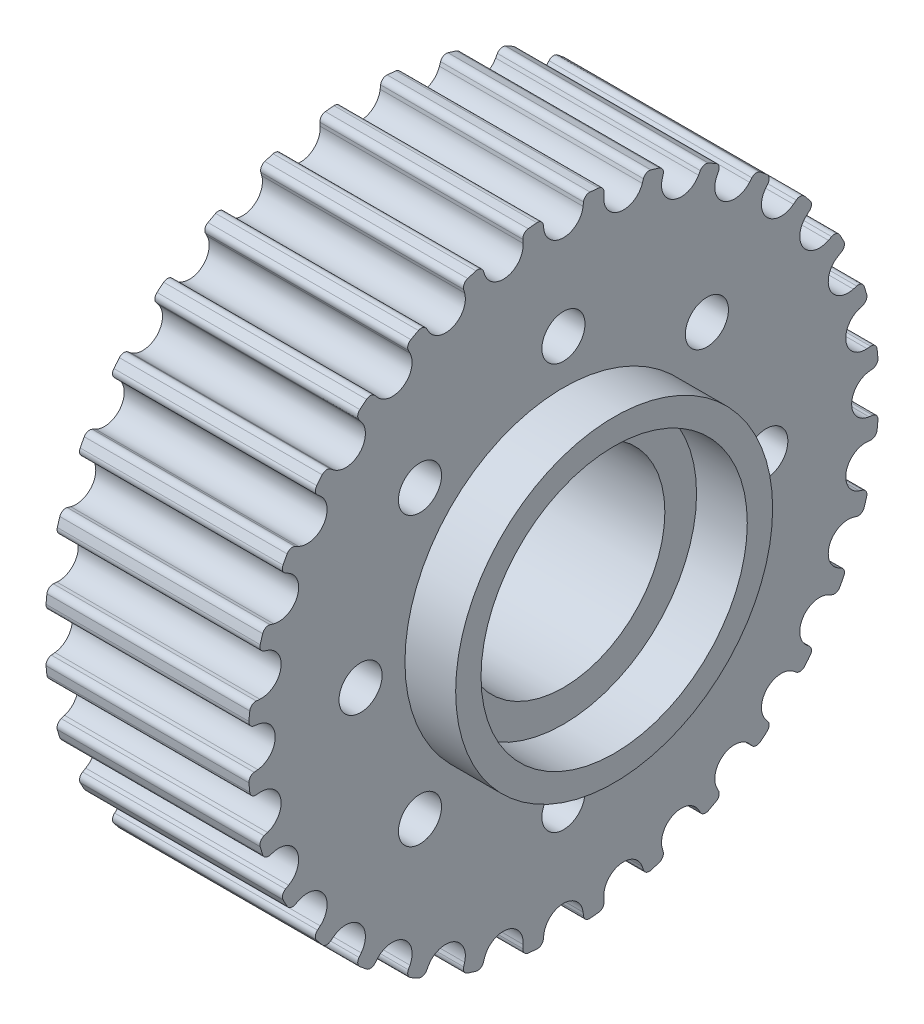
SolidWorks part; units mm, degrees
ref_plane "前视基准面" through (0, 0, 0) normal (0, 0, 1) x (1, 0, 0)
ref_plane "上视基准面" through (0, 0, 0) normal (0, 1, 0) x (1, 0, 0)
ref_plane "右视基准面" through (0, 0, 0) normal (1, 0, 0) x (0, 0, -1)
sketch "草图1" plane through (0, 0, 0) normal (0, 0, 1) x (1, 0, 0)
  line L0 (0, 0) -> (64.8368, 0) construction
  line L1 (0, 2.7506) -> (0, 24.893)
  line L2 (0, 24.893) -> (16, 24.893)
  line L3 (16, 24.893) -> (16, 5.5012)
  line L4 (16, 5.5012) -> (20, 5.5012)
  line L5 (20, 5.5012) -> (20, 2.7506)
  line L6 (20, 2.7506) -> (0, 2.7506)
  dimension "L" = 20
  dimension "B" = 16
  dimension "d" = 5.5012
  dimension "d1" = 11.0024
  dimension "da" = 49.786
revolve "旋转1" add sketch "草图1" angle 360 about L0
ref_axis "基准轴1" through (-1, 0, 0) along (1, 0, 0)
sketch "草图6" plane through (0, 0, 0) normal (1, 0, 0) x (0, 0, -1)
  line L0 (0, 0) -> (0, 30.6512) construction
  line L1 (1.5829, 24.3845) -> (1.5484, 24.1029)
  line L2 (2.5777, 24.7592) -> (2.7744, 26.3607)
  line L3 (-2.5777, 24.7592) -> (-2.7744, 26.3607)
  line L4 (-1.5829, 24.3845) -> (-1.5484, 24.1029)
  circle A0 centre (0, 0) radius 24.893 construction
  circle A1 centre (0, 0) radius 22.733 construction
  arc A2 (-1.5484, 24.1029) -> (1.5484, 24.1029) centre (0, 24.293) ccw
  arc A3 (2.7744, 26.3607) -> (-2.7744, 26.3607) centre (0, 0) ccw
  arc A4 (1.5829, 24.3845) -> (2.0999, 24.8043) centre (2.0594, 24.326) cw
  arc A5 (2.0999, 24.8043) -> (2.5777, 24.7592) centre (0, 0) cw
  arc A6 (-2.0999, 24.8043) -> (-2.5777, 24.7592) centre (0, 0) ccw
  arc A7 (-1.5829, 24.3845) -> (-2.0999, 24.8043) centre (-2.0594, 24.326) ccw
  point P7 (0, 3.25)
  point P8 (0, 28.4912)
  point P15 (1.6388, 24.839)
  dimension "D1" = 45.466
  dimension "ra" = 0.48
  dimension "rf" = 1.56
  dimension "hg" = 2.16
  dimension "D3" = 0.48
  dimension "D4" = 1.6136
  dimension "angle" = 14
  dimension "bw" = 3.25
extrude "切除-拉伸2" cut sketch "草图6" along normal up to next
pattern_circular "阵列(圆周)3" count 32 over 360 about axis through (-1, 0, 0) along (1, 0, 0) of "切除-拉伸2"
sketch "草图8" plane through (16, 0, 0) normal (1, 0, 0) x (0, 0, -1)
  line L64 (1.5829, 24.3845) -> (1.5484, 24.1029)
  line L65 (-1.5484, 24.1029) -> (-1.5829, 24.3845)
  line L66 (-3.2046, 24.2248) -> (-3.1836, 23.9418)
  line L67 (-6.2209, 23.3377) -> (-6.3097, 23.6071)
  line L68 (-7.8691, 23.1341) -> (-7.7933, 22.8607)
  line L69 (-10.6543, 21.6756) -> (-10.794, 21.9226)
  line L70 (-12.2311, 21.1544) -> (-12.1034, 20.901)
  line L71 (-14.6783, 19.1806) -> (-14.8635, 19.3955)
  line L72 (-16.1231, 18.3617) -> (-15.9484, 18.1382)
  line L73 (-18.1382, 15.9484) -> (-18.3617, 16.1231)
  line L74 (-19.3955, 14.8635) -> (-19.1806, 14.6783)
  line L75 (-20.901, 12.1034) -> (-21.1544, 12.2311)
  line L76 (-21.9226, 10.794) -> (-21.6756, 10.6543)
  line L77 (-22.8607, 7.7933) -> (-23.1341, 7.8691)
  line L78 (-23.6071, 6.3097) -> (-23.3377, 6.2209)
  line L79 (-23.9418, 3.1836) -> (-24.2248, 3.2046)
  line L80 (-24.3845, 1.5829) -> (-24.1029, 1.5484)
  line L81 (-24.1029, -1.5484) -> (-24.3845, -1.5829)
  line L82 (-24.2248, -3.2046) -> (-23.9418, -3.1836)
  line L83 (-23.3377, -6.2209) -> (-23.6071, -6.3097)
  line L84 (-23.1341, -7.8691) -> (-22.8607, -7.7933)
  line L85 (-21.6756, -10.6543) -> (-21.9226, -10.794)
  line L86 (-21.1544, -12.2311) -> (-20.901, -12.1034)
  line L87 (-19.1806, -14.6783) -> (-19.3955, -14.8635)
  line L88 (-18.3617, -16.1231) -> (-18.1382, -15.9484)
  line L89 (-15.9484, -18.1382) -> (-16.1231, -18.3617)
  line L90 (-14.8635, -19.3955) -> (-14.6783, -19.1806)
  line L91 (-12.1034, -20.901) -> (-12.2311, -21.1544)
  line L92 (-10.794, -21.9226) -> (-10.6543, -21.6756)
  line L93 (-7.7933, -22.8607) -> (-7.8691, -23.1341)
  line L94 (-6.3097, -23.6071) -> (-6.2209, -23.3377)
  line L95 (-3.1836, -23.9418) -> (-3.2046, -24.2248)
  line L96 (-1.5829, -24.3845) -> (-1.5484, -24.1029)
  line L97 (1.5484, -24.1029) -> (1.5829, -24.3845)
  line L98 (3.2046, -24.2248) -> (3.1836, -23.9418)
  line L99 (6.2209, -23.3377) -> (6.3097, -23.6071)
  line L100 (7.8691, -23.1341) -> (7.7933, -22.8607)
  line L101 (10.6543, -21.6756) -> (10.794, -21.9226)
  line L102 (12.2311, -21.1544) -> (12.1034, -20.901)
  line L103 (14.6783, -19.1806) -> (14.8635, -19.3955)
  line L104 (16.1231, -18.3617) -> (15.9484, -18.1382)
  line L105 (18.1382, -15.9484) -> (18.3617, -16.1231)
  line L106 (19.3955, -14.8635) -> (19.1806, -14.6783)
  line L107 (20.901, -12.1034) -> (21.1544, -12.2311)
  line L108 (21.9226, -10.794) -> (21.6756, -10.6543)
  line L109 (22.8607, -7.7933) -> (23.1341, -7.8691)
  line L110 (23.6071, -6.3097) -> (23.3377, -6.2209)
  line L111 (23.9418, -3.1836) -> (24.2248, -3.2046)
  line L112 (24.3845, -1.5829) -> (24.1029, -1.5484)
  line L113 (24.1029, 1.5484) -> (24.3845, 1.5829)
  line L114 (24.2248, 3.2046) -> (23.9418, 3.1836)
  line L115 (23.3377, 6.2209) -> (23.6071, 6.3097)
  line L116 (23.1341, 7.8691) -> (22.8607, 7.7933)
  line L117 (21.6756, 10.6543) -> (21.9226, 10.794)
  line L118 (21.1544, 12.2311) -> (20.901, 12.1034)
  line L119 (19.1806, 14.6783) -> (19.3955, 14.8635)
  line L120 (18.3617, 16.1231) -> (18.1382, 15.9484)
  line L121 (15.9484, 18.1382) -> (16.1231, 18.3617)
  line L122 (14.8635, 19.3955) -> (14.6783, 19.1806)
  line L123 (12.1034, 20.901) -> (12.2311, 21.1544)
  line L124 (10.794, 21.9226) -> (10.6543, 21.6756)
  line L125 (7.7933, 22.8607) -> (7.8691, 23.1341)
  line L126 (6.3097, 23.6071) -> (6.2209, 23.3377)
  line L127 (3.1836, 23.9418) -> (3.2046, 24.2248)
  line L128 (1.5829, 24.3845) -> (1.5484, 24.1029)
  line L129 (-1.5484, 24.1029) -> (-1.5829, 24.3845)
  line L130 (-3.2046, 24.2248) -> (-3.1836, 23.9418)
  line L131 (-6.2209, 23.3377) -> (-6.3097, 23.6071)
  line L132 (-7.8691, 23.1341) -> (-7.7933, 22.8607)
  line L133 (-10.6543, 21.6756) -> (-10.794, 21.9226)
  line L134 (-12.2311, 21.1544) -> (-12.1034, 20.901)
  line L135 (-14.6783, 19.1806) -> (-14.8635, 19.3955)
  line L136 (-16.1231, 18.3617) -> (-15.9484, 18.1382)
  line L137 (-18.1382, 15.9484) -> (-18.3617, 16.1231)
  line L138 (-19.3955, 14.8635) -> (-19.1806, 14.6783)
  line L139 (-20.901, 12.1034) -> (-21.1544, 12.2311)
  line L140 (-21.9226, 10.794) -> (-21.6756, 10.6543)
  line L141 (-22.8607, 7.7933) -> (-23.1341, 7.8691)
  line L142 (-23.6071, 6.3097) -> (-23.3377, 6.2209)
  line L143 (-23.9418, 3.1836) -> (-24.2248, 3.2046)
  line L144 (-24.3845, 1.5829) -> (-24.1029, 1.5484)
  line L145 (-24.1029, -1.5484) -> (-24.3845, -1.5829)
  line L146 (-24.2248, -3.2046) -> (-23.9418, -3.1836)
  line L147 (-23.3377, -6.2209) -> (-23.6071, -6.3097)
  line L148 (-23.1341, -7.8691) -> (-22.8607, -7.7933)
  line L149 (-21.6756, -10.6543) -> (-21.9226, -10.794)
  line L150 (-21.1544, -12.2311) -> (-20.901, -12.1034)
  line L151 (-19.1806, -14.6783) -> (-19.3955, -14.8635)
  line L152 (-18.3617, -16.1231) -> (-18.1382, -15.9484)
  line L153 (-15.9484, -18.1382) -> (-16.1231, -18.3617)
  line L154 (-14.8635, -19.3955) -> (-14.6783, -19.1806)
  line L155 (-12.1034, -20.901) -> (-12.2311, -21.1544)
  line L156 (-10.794, -21.9226) -> (-10.6543, -21.6756)
  line L157 (-7.7933, -22.8607) -> (-7.8691, -23.1341)
  line L158 (-6.3097, -23.6071) -> (-6.2209, -23.3377)
  line L159 (-3.1836, -23.9418) -> (-3.2046, -24.2248)
  line L160 (-1.5829, -24.3845) -> (-1.5484, -24.1029)
  line L161 (1.5484, -24.1029) -> (1.5829, -24.3845)
  line L162 (3.2046, -24.2248) -> (3.1836, -23.9418)
  line L163 (6.2209, -23.3377) -> (6.3097, -23.6071)
  line L164 (7.8691, -23.1341) -> (7.7933, -22.8607)
  line L165 (10.6543, -21.6756) -> (10.794, -21.9226)
  line L166 (12.2311, -21.1544) -> (12.1034, -20.901)
  line L167 (14.6783, -19.1806) -> (14.8635, -19.3955)
  line L168 (16.1231, -18.3617) -> (15.9484, -18.1382)
  line L169 (18.1382, -15.9484) -> (18.3617, -16.1231)
  line L170 (19.3955, -14.8635) -> (19.1806, -14.6783)
  line L171 (20.901, -12.1034) -> (21.1544, -12.2311)
  line L172 (21.9226, -10.794) -> (21.6756, -10.6543)
  line L173 (22.8607, -7.7933) -> (23.1341, -7.8691)
  line L174 (23.6071, -6.3097) -> (23.3377, -6.2209)
  line L175 (23.9418, -3.1836) -> (24.2248, -3.2046)
  line L176 (24.3845, -1.5829) -> (24.1029, -1.5484)
  line L177 (24.1029, 1.5484) -> (24.3845, 1.5829)
  line L178 (24.2248, 3.2046) -> (23.9418, 3.1836)
  line L179 (23.3377, 6.2209) -> (23.6071, 6.3097)
  line L180 (23.1341, 7.8691) -> (22.8607, 7.7933)
  line L181 (21.6756, 10.6543) -> (21.9226, 10.794)
  line L182 (21.1544, 12.2311) -> (20.901, 12.1034)
  line L183 (19.1806, 14.6783) -> (19.3955, 14.8635)
  line L184 (18.3617, 16.1231) -> (18.1382, 15.9484)
  line L185 (15.9484, 18.1382) -> (16.1231, 18.3617)
  line L186 (14.8635, 19.3955) -> (14.6783, 19.1806)
  line L187 (12.1034, 20.901) -> (12.2311, 21.1544)
  line L188 (10.794, 21.9226) -> (10.6543, 21.6756)
  line L189 (7.7933, 22.8607) -> (7.8691, 23.1341)
  line L190 (6.3097, 23.6071) -> (6.2209, 23.3377)
  line L191 (3.1836, 23.9418) -> (3.2046, 24.2248)
  circle A0 centre (0, 0) radius 12.5
  arc A128 (3.2046, 24.2248) -> (2.7796, 24.7373) centre (2.726, 24.2603) ccw
  arc A129 (2.7796, 24.7373) -> (2.0999, 24.8043) centre (0, 0) ccw
  arc A130 (2.0999, 24.8043) -> (1.5829, 24.3845) centre (2.0594, 24.326) ccw
  arc A131 (-1.5484, 24.1029) -> (1.5484, 24.1029) centre (0, 24.293) ccw
  arc A132 (-1.5829, 24.3845) -> (-2.0999, 24.8043) centre (-2.0594, 24.326) ccw
  arc A133 (-2.0999, 24.8043) -> (-2.7796, 24.7373) centre (0, 0) ccw
  arc A134 (-2.7796, 24.7373) -> (-3.2046, 24.2248) centre (-2.726, 24.2603) ccw
  arc A135 (-6.2209, 23.3377) -> (-3.1836, 23.9418) centre (-4.7393, 23.8262) ccw
  arc A136 (-6.3097, 23.6071) -> (-6.8986, 23.918) centre (-6.7656, 23.4568) ccw
  arc A137 (-6.8986, 23.918) -> (-7.5522, 23.7197) centre (0, 0) ccw
  arc A138 (-7.5522, 23.7197) -> (-7.8691, 23.1341) centre (-7.4065, 23.2624) ccw
  arc A139 (-10.6543, 21.6756) -> (-7.7933, 22.8607) centre (-9.2965, 22.4438) ccw
  arc A140 (-10.794, 21.9226) -> (-11.4322, 22.1126) centre (-11.2118, 21.6862) ccw
  arc A141 (-11.4322, 22.1126) -> (-12.0345, 21.7906) centre (0, 0) ccw
  arc A142 (-12.0345, 21.7906) -> (-12.2311, 21.1544) centre (-11.8025, 21.3704) ccw
  arc A143 (-14.6783, 19.1806) -> (-12.1034, 20.901) centre (-13.4965, 20.1989) ccw
  arc A144 (-14.8635, 19.3955) -> (-15.5265, 19.4574) centre (-15.2271, 19.0822) ccw
  arc A145 (-15.5265, 19.4574) -> (-16.0544, 19.0241) centre (0, 0) ccw
  arc A146 (-16.0544, 19.0241) -> (-16.1231, 18.3617) centre (-15.7449, 18.6573) ccw
  arc A147 (-18.1382, 15.9484) -> (-15.9484, 18.1382) centre (-17.1777, 17.1777) ccw
  arc A148 (-18.3617, 16.1231) -> (-19.0241, 16.0544) centre (-18.6573, 15.7449) ccw
  arc A149 (-19.0241, 16.0544) -> (-19.4574, 15.5265) centre (0, 0) ccw
  arc A150 (-19.4574, 15.5265) -> (-19.3955, 14.8635) centre (-19.0822, 15.2271) ccw
  arc A151 (-20.901, 12.1034) -> (-19.1806, 14.6783) centre (-20.1989, 13.4965) ccw
  arc A152 (-21.1544, 12.2311) -> (-21.7906, 12.0345) centre (-21.3704, 11.8025) ccw
  arc A153 (-21.7906, 12.0345) -> (-22.1126, 11.4322) centre (0, 0) ccw
  arc A154 (-22.1126, 11.4322) -> (-21.9226, 10.794) centre (-21.6862, 11.2118) ccw
  arc A155 (-22.8607, 7.7933) -> (-21.6756, 10.6543) centre (-22.4438, 9.2965) ccw
  arc A156 (-23.1341, 7.8691) -> (-23.7197, 7.5522) centre (-23.2624, 7.4065) ccw
  arc A157 (-23.7197, 7.5522) -> (-23.918, 6.8986) centre (0, 0) ccw
  arc A158 (-23.918, 6.8986) -> (-23.6071, 6.3097) centre (-23.4568, 6.7656) ccw
  arc A159 (-23.9418, 3.1836) -> (-23.3377, 6.2209) centre (-23.8262, 4.7393) ccw
  arc A160 (-24.2248, 3.2046) -> (-24.7373, 2.7796) centre (-24.2603, 2.726) ccw
  arc A161 (-24.7373, 2.7796) -> (-24.8043, 2.0999) centre (0, 0) ccw
  arc A162 (-24.8043, 2.0999) -> (-24.3845, 1.5829) centre (-24.326, 2.0594) ccw
  arc A163 (-24.1029, -1.5484) -> (-24.1029, 1.5484) centre (-24.293, 0) ccw
  arc A164 (-24.3845, -1.5829) -> (-24.8043, -2.0999) centre (-24.326, -2.0594) ccw
  arc A165 (-24.8043, -2.0999) -> (-24.7373, -2.7796) centre (0, 0) ccw
  arc A166 (-24.7373, -2.7796) -> (-24.2248, -3.2046) centre (-24.2603, -2.726) ccw
  arc A167 (-23.3377, -6.2209) -> (-23.9418, -3.1836) centre (-23.8262, -4.7393) ccw
  arc A168 (-23.6071, -6.3097) -> (-23.918, -6.8986) centre (-23.4568, -6.7656) ccw
  arc A169 (-23.918, -6.8986) -> (-23.7197, -7.5522) centre (0, 0) ccw
  arc A170 (-23.7197, -7.5522) -> (-23.1341, -7.8691) centre (-23.2624, -7.4065) ccw
  arc A171 (-21.6756, -10.6543) -> (-22.8607, -7.7933) centre (-22.4438, -9.2965) ccw
  arc A172 (-21.9226, -10.794) -> (-22.1126, -11.4322) centre (-21.6862, -11.2118) ccw
  arc A173 (-22.1126, -11.4322) -> (-21.7906, -12.0345) centre (0, 0) ccw
  arc A174 (-21.7906, -12.0345) -> (-21.1544, -12.2311) centre (-21.3704, -11.8025) ccw
  arc A175 (-19.1806, -14.6783) -> (-20.901, -12.1034) centre (-20.1989, -13.4965) ccw
  arc A176 (-19.3955, -14.8635) -> (-19.4574, -15.5265) centre (-19.0822, -15.2271) ccw
  arc A177 (-19.4574, -15.5265) -> (-19.0241, -16.0544) centre (0, 0) ccw
  arc A178 (-19.0241, -16.0544) -> (-18.3617, -16.1231) centre (-18.6573, -15.7449) ccw
  arc A179 (-15.9484, -18.1382) -> (-18.1382, -15.9484) centre (-17.1777, -17.1777) ccw
  arc A180 (-16.1231, -18.3617) -> (-16.0544, -19.0241) centre (-15.7449, -18.6573) ccw
  arc A181 (-16.0544, -19.0241) -> (-15.5265, -19.4574) centre (0, 0) ccw
  arc A182 (-15.5265, -19.4574) -> (-14.8635, -19.3955) centre (-15.2271, -19.0822) ccw
  arc A183 (-12.1034, -20.901) -> (-14.6783, -19.1806) centre (-13.4965, -20.1989) ccw
  arc A184 (-12.2311, -21.1544) -> (-12.0345, -21.7906) centre (-11.8025, -21.3704) ccw
  arc A185 (-12.0345, -21.7906) -> (-11.4322, -22.1126) centre (0, 0) ccw
  arc A186 (-11.4322, -22.1126) -> (-10.794, -21.9226) centre (-11.2118, -21.6862) ccw
  arc A187 (-7.7933, -22.8607) -> (-10.6543, -21.6756) centre (-9.2965, -22.4438) ccw
  arc A188 (-7.8691, -23.1341) -> (-7.5522, -23.7197) centre (-7.4065, -23.2624) ccw
  arc A189 (-7.5522, -23.7197) -> (-6.8986, -23.918) centre (0, 0) ccw
  arc A190 (-6.8986, -23.918) -> (-6.3097, -23.6071) centre (-6.7656, -23.4568) ccw
  arc A191 (-3.1836, -23.9418) -> (-6.2209, -23.3377) centre (-4.7393, -23.8262) ccw
  arc A192 (-3.2046, -24.2248) -> (-2.7796, -24.7373) centre (-2.726, -24.2603) ccw
  arc A193 (-2.7796, -24.7373) -> (-2.0999, -24.8043) centre (0, 0) ccw
  arc A194 (-2.0999, -24.8043) -> (-1.5829, -24.3845) centre (-2.0594, -24.326) ccw
  arc A195 (1.5484, -24.1029) -> (-1.5484, -24.1029) centre (0, -24.293) ccw
  arc A196 (1.5829, -24.3845) -> (2.0999, -24.8043) centre (2.0594, -24.326) ccw
  arc A197 (2.0999, -24.8043) -> (2.7796, -24.7373) centre (0, 0) ccw
  arc A198 (2.7796, -24.7373) -> (3.2046, -24.2248) centre (2.726, -24.2603) ccw
  arc A199 (6.2209, -23.3377) -> (3.1836, -23.9418) centre (4.7393, -23.8262) ccw
  arc A200 (6.3097, -23.6071) -> (6.8986, -23.918) centre (6.7656, -23.4568) ccw
  arc A201 (6.8986, -23.918) -> (7.5522, -23.7197) centre (0, 0) ccw
  arc A202 (7.5522, -23.7197) -> (7.8691, -23.1341) centre (7.4065, -23.2624) ccw
  arc A203 (10.6543, -21.6756) -> (7.7933, -22.8607) centre (9.2965, -22.4438) ccw
  arc A204 (10.794, -21.9226) -> (11.4322, -22.1126) centre (11.2118, -21.6862) ccw
  arc A205 (11.4322, -22.1126) -> (12.0345, -21.7906) centre (0, 0) ccw
  arc A206 (12.0345, -21.7906) -> (12.2311, -21.1544) centre (11.8025, -21.3704) ccw
  arc A207 (14.6783, -19.1806) -> (12.1034, -20.901) centre (13.4965, -20.1989) ccw
  arc A208 (14.8635, -19.3955) -> (15.5265, -19.4574) centre (15.2271, -19.0822) ccw
  arc A209 (15.5265, -19.4574) -> (16.0544, -19.0241) centre (0, 0) ccw
  arc A210 (16.0544, -19.0241) -> (16.1231, -18.3617) centre (15.7449, -18.6573) ccw
  arc A211 (18.1382, -15.9484) -> (15.9484, -18.1382) centre (17.1777, -17.1777) ccw
  arc A212 (18.3617, -16.1231) -> (19.0241, -16.0544) centre (18.6573, -15.7449) ccw
  arc A213 (19.0241, -16.0544) -> (19.4574, -15.5265) centre (0, 0) ccw
  arc A214 (19.4574, -15.5265) -> (19.3955, -14.8635) centre (19.0822, -15.2271) ccw
  arc A215 (20.901, -12.1034) -> (19.1806, -14.6783) centre (20.1989, -13.4965) ccw
  arc A216 (21.1544, -12.2311) -> (21.7906, -12.0345) centre (21.3704, -11.8025) ccw
  arc A217 (21.7906, -12.0345) -> (22.1126, -11.4322) centre (0, 0) ccw
  arc A218 (22.1126, -11.4322) -> (21.9226, -10.794) centre (21.6862, -11.2118) ccw
  arc A219 (22.8607, -7.7933) -> (21.6756, -10.6543) centre (22.4438, -9.2965) ccw
  arc A220 (23.1341, -7.8691) -> (23.7197, -7.5522) centre (23.2624, -7.4065) ccw
  arc A221 (23.7197, -7.5522) -> (23.918, -6.8986) centre (0, 0) ccw
  arc A222 (23.918, -6.8986) -> (23.6071, -6.3097) centre (23.4568, -6.7656) ccw
  arc A223 (23.9418, -3.1836) -> (23.3377, -6.2209) centre (23.8262, -4.7393) ccw
  arc A224 (24.2248, -3.2046) -> (24.7373, -2.7796) centre (24.2603, -2.726) ccw
  arc A225 (24.7373, -2.7796) -> (24.8043, -2.0999) centre (0, 0) ccw
  arc A226 (24.8043, -2.0999) -> (24.3845, -1.5829) centre (24.326, -2.0594) ccw
  arc A227 (24.1029, 1.5484) -> (24.1029, -1.5484) centre (24.293, 0) ccw
  arc A228 (24.3845, 1.5829) -> (24.8043, 2.0999) centre (24.326, 2.0594) ccw
  arc A229 (24.8043, 2.0999) -> (24.7373, 2.7796) centre (0, 0) ccw
  arc A230 (24.7373, 2.7796) -> (24.2248, 3.2046) centre (24.2603, 2.726) ccw
  arc A231 (23.3377, 6.2209) -> (23.9418, 3.1836) centre (23.8262, 4.7393) ccw
  arc A232 (23.6071, 6.3097) -> (23.918, 6.8986) centre (23.4568, 6.7656) ccw
  arc A233 (23.918, 6.8986) -> (23.7197, 7.5522) centre (0, 0) ccw
  arc A234 (23.7197, 7.5522) -> (23.1341, 7.8691) centre (23.2624, 7.4065) ccw
  arc A235 (21.6756, 10.6543) -> (22.8607, 7.7933) centre (22.4438, 9.2965) ccw
  arc A236 (21.9226, 10.794) -> (22.1126, 11.4322) centre (21.6862, 11.2118) ccw
  arc A237 (22.1126, 11.4322) -> (21.7906, 12.0345) centre (0, 0) ccw
  arc A238 (21.7906, 12.0345) -> (21.1544, 12.2311) centre (21.3704, 11.8025) ccw
  arc A239 (19.1806, 14.6783) -> (20.901, 12.1034) centre (20.1989, 13.4965) ccw
  arc A240 (19.3955, 14.8635) -> (19.4574, 15.5265) centre (19.0822, 15.2271) ccw
  arc A241 (19.4574, 15.5265) -> (19.0241, 16.0544) centre (0, 0) ccw
  arc A242 (19.0241, 16.0544) -> (18.3617, 16.1231) centre (18.6573, 15.7449) ccw
  arc A243 (15.9484, 18.1382) -> (18.1382, 15.9484) centre (17.1777, 17.1777) ccw
  arc A244 (16.1231, 18.3617) -> (16.0544, 19.0241) centre (15.7449, 18.6573) ccw
  arc A245 (16.0544, 19.0241) -> (15.5265, 19.4574) centre (0, 0) ccw
  arc A246 (15.5265, 19.4574) -> (14.8635, 19.3955) centre (15.2271, 19.0822) ccw
  arc A247 (12.1034, 20.901) -> (14.6783, 19.1806) centre (13.4965, 20.1989) ccw
  arc A248 (12.2311, 21.1544) -> (12.0345, 21.7906) centre (11.8025, 21.3704) ccw
  arc A249 (12.0345, 21.7906) -> (11.4322, 22.1126) centre (0, 0) ccw
  arc A250 (11.4322, 22.1126) -> (10.794, 21.9226) centre (11.2118, 21.6862) ccw
  arc A251 (7.7933, 22.8607) -> (10.6543, 21.6756) centre (9.2965, 22.4438) ccw
  arc A252 (7.8691, 23.1341) -> (7.5522, 23.7197) centre (7.4065, 23.2624) ccw
  arc A253 (7.5522, 23.7197) -> (6.8986, 23.918) centre (0, 0) ccw
  arc A254 (6.8986, 23.918) -> (6.3097, 23.6071) centre (6.7656, 23.4568) ccw
  arc A255 (3.1836, 23.9418) -> (6.2209, 23.3377) centre (4.7393, 23.8262) ccw
  arc A256 (3.2046, 24.2248) -> (2.7796, 24.7373) centre (2.726, 24.2603) ccw
  arc A257 (2.7796, 24.7373) -> (2.0999, 24.8043) centre (0, 0) ccw
  arc A258 (2.0999, 24.8043) -> (1.5829, 24.3845) centre (2.0594, 24.326) ccw
  arc A259 (-1.5484, 24.1029) -> (1.5484, 24.1029) centre (0, 24.293) ccw
  arc A260 (-1.5829, 24.3845) -> (-2.0999, 24.8043) centre (-2.0594, 24.326) ccw
  arc A261 (-2.0999, 24.8043) -> (-2.7796, 24.7373) centre (0, 0) ccw
  arc A262 (-2.7796, 24.7373) -> (-3.2046, 24.2248) centre (-2.726, 24.2603) ccw
  arc A263 (-6.2209, 23.3377) -> (-3.1836, 23.9418) centre (-4.7393, 23.8262) ccw
  arc A264 (-6.3097, 23.6071) -> (-6.8986, 23.918) centre (-6.7656, 23.4568) ccw
  arc A265 (-6.8986, 23.918) -> (-7.5522, 23.7197) centre (0, 0) ccw
  arc A266 (-7.5522, 23.7197) -> (-7.8691, 23.1341) centre (-7.4065, 23.2624) ccw
  arc A267 (-10.6543, 21.6756) -> (-7.7933, 22.8607) centre (-9.2965, 22.4438) ccw
  arc A268 (-10.794, 21.9226) -> (-11.4322, 22.1126) centre (-11.2118, 21.6862) ccw
  arc A269 (-11.4322, 22.1126) -> (-12.0345, 21.7906) centre (0, 0) ccw
  arc A270 (-12.0345, 21.7906) -> (-12.2311, 21.1544) centre (-11.8025, 21.3704) ccw
  arc A271 (-14.6783, 19.1806) -> (-12.1034, 20.901) centre (-13.4965, 20.1989) ccw
  arc A272 (-14.8635, 19.3955) -> (-15.5265, 19.4574) centre (-15.2271, 19.0822) ccw
  arc A273 (-15.5265, 19.4574) -> (-16.0544, 19.0241) centre (0, 0) ccw
  arc A274 (-16.0544, 19.0241) -> (-16.1231, 18.3617) centre (-15.7449, 18.6573) ccw
  arc A275 (-18.1382, 15.9484) -> (-15.9484, 18.1382) centre (-17.1777, 17.1777) ccw
  arc A276 (-18.3617, 16.1231) -> (-19.0241, 16.0544) centre (-18.6573, 15.7449) ccw
  arc A277 (-19.0241, 16.0544) -> (-19.4574, 15.5265) centre (0, 0) ccw
  arc A278 (-19.4574, 15.5265) -> (-19.3955, 14.8635) centre (-19.0822, 15.2271) ccw
  arc A279 (-20.901, 12.1034) -> (-19.1806, 14.6783) centre (-20.1989, 13.4965) ccw
  arc A280 (-21.1544, 12.2311) -> (-21.7906, 12.0345) centre (-21.3704, 11.8025) ccw
  arc A281 (-21.7906, 12.0345) -> (-22.1126, 11.4322) centre (0, 0) ccw
  arc A282 (-22.1126, 11.4322) -> (-21.9226, 10.794) centre (-21.6862, 11.2118) ccw
  arc A283 (-22.8607, 7.7933) -> (-21.6756, 10.6543) centre (-22.4438, 9.2965) ccw
  arc A284 (-23.1341, 7.8691) -> (-23.7197, 7.5522) centre (-23.2624, 7.4065) ccw
  arc A285 (-23.7197, 7.5522) -> (-23.918, 6.8986) centre (0, 0) ccw
  arc A286 (-23.918, 6.8986) -> (-23.6071, 6.3097) centre (-23.4568, 6.7656) ccw
  arc A287 (-23.9418, 3.1836) -> (-23.3377, 6.2209) centre (-23.8262, 4.7393) ccw
  arc A288 (-24.2248, 3.2046) -> (-24.7373, 2.7796) centre (-24.2603, 2.726) ccw
  arc A289 (-24.7373, 2.7796) -> (-24.8043, 2.0999) centre (0, 0) ccw
  arc A290 (-24.8043, 2.0999) -> (-24.3845, 1.5829) centre (-24.326, 2.0594) ccw
  arc A291 (-24.1029, -1.5484) -> (-24.1029, 1.5484) centre (-24.293, 0) ccw
  arc A292 (-24.3845, -1.5829) -> (-24.8043, -2.0999) centre (-24.326, -2.0594) ccw
  arc A293 (-24.8043, -2.0999) -> (-24.7373, -2.7796) centre (0, 0) ccw
  arc A294 (-24.7373, -2.7796) -> (-24.2248, -3.2046) centre (-24.2603, -2.726) ccw
  arc A295 (-23.3377, -6.2209) -> (-23.9418, -3.1836) centre (-23.8262, -4.7393) ccw
  arc A296 (-23.6071, -6.3097) -> (-23.918, -6.8986) centre (-23.4568, -6.7656) ccw
  arc A297 (-23.918, -6.8986) -> (-23.7197, -7.5522) centre (0, 0) ccw
  arc A298 (-23.7197, -7.5522) -> (-23.1341, -7.8691) centre (-23.2624, -7.4065) ccw
  arc A299 (-21.6756, -10.6543) -> (-22.8607, -7.7933) centre (-22.4438, -9.2965) ccw
  arc A300 (-21.9226, -10.794) -> (-22.1126, -11.4322) centre (-21.6862, -11.2118) ccw
  arc A301 (-22.1126, -11.4322) -> (-21.7906, -12.0345) centre (0, 0) ccw
  arc A302 (-21.7906, -12.0345) -> (-21.1544, -12.2311) centre (-21.3704, -11.8025) ccw
  arc A303 (-19.1806, -14.6783) -> (-20.901, -12.1034) centre (-20.1989, -13.4965) ccw
  arc A304 (-19.3955, -14.8635) -> (-19.4574, -15.5265) centre (-19.0822, -15.2271) ccw
  arc A305 (-19.4574, -15.5265) -> (-19.0241, -16.0544) centre (0, 0) ccw
  arc A306 (-19.0241, -16.0544) -> (-18.3617, -16.1231) centre (-18.6573, -15.7449) ccw
  arc A307 (-15.9484, -18.1382) -> (-18.1382, -15.9484) centre (-17.1777, -17.1777) ccw
  arc A308 (-16.1231, -18.3617) -> (-16.0544, -19.0241) centre (-15.7449, -18.6573) ccw
  arc A309 (-16.0544, -19.0241) -> (-15.5265, -19.4574) centre (0, 0) ccw
  arc A310 (-15.5265, -19.4574) -> (-14.8635, -19.3955) centre (-15.2271, -19.0822) ccw
  arc A311 (-12.1034, -20.901) -> (-14.6783, -19.1806) centre (-13.4965, -20.1989) ccw
  arc A312 (-12.2311, -21.1544) -> (-12.0345, -21.7906) centre (-11.8025, -21.3704) ccw
  arc A313 (-12.0345, -21.7906) -> (-11.4322, -22.1126) centre (0, 0) ccw
  arc A314 (-11.4322, -22.1126) -> (-10.794, -21.9226) centre (-11.2118, -21.6862) ccw
  arc A315 (-7.7933, -22.8607) -> (-10.6543, -21.6756) centre (-9.2965, -22.4438) ccw
  arc A316 (-7.8691, -23.1341) -> (-7.5522, -23.7197) centre (-7.4065, -23.2624) ccw
  arc A317 (-7.5522, -23.7197) -> (-6.8986, -23.918) centre (0, 0) ccw
  arc A318 (-6.8986, -23.918) -> (-6.3097, -23.6071) centre (-6.7656, -23.4568) ccw
  arc A319 (-3.1836, -23.9418) -> (-6.2209, -23.3377) centre (-4.7393, -23.8262) ccw
  arc A320 (-3.2046, -24.2248) -> (-2.7796, -24.7373) centre (-2.726, -24.2603) ccw
  arc A321 (-2.7796, -24.7373) -> (-2.0999, -24.8043) centre (0, 0) ccw
  arc A322 (-2.0999, -24.8043) -> (-1.5829, -24.3845) centre (-2.0594, -24.326) ccw
  arc A323 (1.5484, -24.1029) -> (-1.5484, -24.1029) centre (0, -24.293) ccw
  arc A324 (1.5829, -24.3845) -> (2.0999, -24.8043) centre (2.0594, -24.326) ccw
  arc A325 (2.0999, -24.8043) -> (2.7796, -24.7373) centre (0, 0) ccw
  arc A326 (2.7796, -24.7373) -> (3.2046, -24.2248) centre (2.726, -24.2603) ccw
  arc A327 (6.2209, -23.3377) -> (3.1836, -23.9418) centre (4.7393, -23.8262) ccw
  arc A328 (6.3097, -23.6071) -> (6.8986, -23.918) centre (6.7656, -23.4568) ccw
  arc A329 (6.8986, -23.918) -> (7.5522, -23.7197) centre (0, 0) ccw
  arc A330 (7.5522, -23.7197) -> (7.8691, -23.1341) centre (7.4065, -23.2624) ccw
  arc A331 (10.6543, -21.6756) -> (7.7933, -22.8607) centre (9.2965, -22.4438) ccw
  arc A332 (10.794, -21.9226) -> (11.4322, -22.1126) centre (11.2118, -21.6862) ccw
  arc A333 (11.4322, -22.1126) -> (12.0345, -21.7906) centre (0, 0) ccw
  arc A334 (12.0345, -21.7906) -> (12.2311, -21.1544) centre (11.8025, -21.3704) ccw
  arc A335 (14.6783, -19.1806) -> (12.1034, -20.901) centre (13.4965, -20.1989) ccw
  arc A336 (14.8635, -19.3955) -> (15.5265, -19.4574) centre (15.2271, -19.0822) ccw
  arc A337 (15.5265, -19.4574) -> (16.0544, -19.0241) centre (0, 0) ccw
  arc A338 (16.0544, -19.0241) -> (16.1231, -18.3617) centre (15.7449, -18.6573) ccw
  arc A339 (18.1382, -15.9484) -> (15.9484, -18.1382) centre (17.1777, -17.1777) ccw
  arc A340 (18.3617, -16.1231) -> (19.0241, -16.0544) centre (18.6573, -15.7449) ccw
  arc A341 (19.0241, -16.0544) -> (19.4574, -15.5265) centre (0, 0) ccw
  arc A342 (19.4574, -15.5265) -> (19.3955, -14.8635) centre (19.0822, -15.2271) ccw
  arc A343 (20.901, -12.1034) -> (19.1806, -14.6783) centre (20.1989, -13.4965) ccw
  arc A344 (21.1544, -12.2311) -> (21.7906, -12.0345) centre (21.3704, -11.8025) ccw
  arc A345 (21.7906, -12.0345) -> (22.1126, -11.4322) centre (0, 0) ccw
  arc A346 (22.1126, -11.4322) -> (21.9226, -10.794) centre (21.6862, -11.2118) ccw
  arc A347 (22.8607, -7.7933) -> (21.6756, -10.6543) centre (22.4438, -9.2965) ccw
  arc A348 (23.1341, -7.8691) -> (23.7197, -7.5522) centre (23.2624, -7.4065) ccw
  arc A349 (23.7197, -7.5522) -> (23.918, -6.8986) centre (0, 0) ccw
  arc A350 (23.918, -6.8986) -> (23.6071, -6.3097) centre (23.4568, -6.7656) ccw
  arc A351 (23.9418, -3.1836) -> (23.3377, -6.2209) centre (23.8262, -4.7393) ccw
  arc A352 (24.2248, -3.2046) -> (24.7373, -2.7796) centre (24.2603, -2.726) ccw
  arc A353 (24.7373, -2.7796) -> (24.8043, -2.0999) centre (0, 0) ccw
  arc A354 (24.8043, -2.0999) -> (24.3845, -1.5829) centre (24.326, -2.0594) ccw
  arc A355 (24.1029, 1.5484) -> (24.1029, -1.5484) centre (24.293, 0) ccw
  arc A356 (24.3845, 1.5829) -> (24.8043, 2.0999) centre (24.326, 2.0594) ccw
  arc A357 (24.8043, 2.0999) -> (24.7373, 2.7796) centre (0, 0) ccw
  arc A358 (24.7373, 2.7796) -> (24.2248, 3.2046) centre (24.2603, 2.726) ccw
  arc A359 (23.3377, 6.2209) -> (23.9418, 3.1836) centre (23.8262, 4.7393) ccw
  arc A360 (23.6071, 6.3097) -> (23.918, 6.8986) centre (23.4568, 6.7656) ccw
  arc A361 (23.918, 6.8986) -> (23.7197, 7.5522) centre (0, 0) ccw
  arc A362 (23.7197, 7.5522) -> (23.1341, 7.8691) centre (23.2624, 7.4065) ccw
  arc A363 (21.6756, 10.6543) -> (22.8607, 7.7933) centre (22.4438, 9.2965) ccw
  arc A364 (21.9226, 10.794) -> (22.1126, 11.4322) centre (21.6862, 11.2118) ccw
  arc A365 (22.1126, 11.4322) -> (21.7906, 12.0345) centre (0, 0) ccw
  arc A366 (21.7906, 12.0345) -> (21.1544, 12.2311) centre (21.3704, 11.8025) ccw
  arc A367 (19.1806, 14.6783) -> (20.901, 12.1034) centre (20.1989, 13.4965) ccw
  arc A368 (19.3955, 14.8635) -> (19.4574, 15.5265) centre (19.0822, 15.2271) ccw
  arc A369 (19.4574, 15.5265) -> (19.0241, 16.0544) centre (0, 0) ccw
  arc A370 (19.0241, 16.0544) -> (18.3617, 16.1231) centre (18.6573, 15.7449) ccw
  arc A371 (15.9484, 18.1382) -> (18.1382, 15.9484) centre (17.1777, 17.1777) ccw
  arc A372 (16.1231, 18.3617) -> (16.0544, 19.0241) centre (15.7449, 18.6573) ccw
  arc A373 (16.0544, 19.0241) -> (15.5265, 19.4574) centre (0, 0) ccw
  arc A374 (15.5265, 19.4574) -> (14.8635, 19.3955) centre (15.2271, 19.0822) ccw
  arc A375 (12.1034, 20.901) -> (14.6783, 19.1806) centre (13.4965, 20.1989) ccw
  arc A376 (12.2311, 21.1544) -> (12.0345, 21.7906) centre (11.8025, 21.3704) ccw
  arc A377 (12.0345, 21.7906) -> (11.4322, 22.1126) centre (0, 0) ccw
  arc A378 (11.4322, 22.1126) -> (10.794, 21.9226) centre (11.2118, 21.6862) ccw
  arc A379 (7.7933, 22.8607) -> (10.6543, 21.6756) centre (9.2965, 22.4438) ccw
  arc A380 (7.8691, 23.1341) -> (7.5522, 23.7197) centre (7.4065, 23.2624) ccw
  arc A381 (7.5522, 23.7197) -> (6.8986, 23.918) centre (0, 0) ccw
  arc A382 (6.8986, 23.918) -> (6.3097, 23.6071) centre (6.7656, 23.4568) ccw
  arc A383 (3.1836, 23.9418) -> (6.2209, 23.3377) centre (4.7393, 23.8262) ccw
  dimension "D2" = 25
  dimension "D1" = 0
extrude "凸台-拉伸1" add sketch "草图8" along normal blind 4 contours A0
sketch "草图9" plane through (20, 0, 0) normal (1, 0, 0) x (0, 0, -1)
  circle A0 centre (0, 0) radius 10.5
  dimension "D1" = 21
extrude "切除-拉伸3" cut sketch "草图9" against normal blind 4
sketch "草图10" plane through (16, 0, 0) normal (1, 0, 0) x (0, 0, -1)
  circle A0 centre (0, 0) radius 8
  dimension "D1" = 16
extrude "切除-拉伸4" cut sketch "草图10" against normal blind 58.1
ref_plane "基准面1" through (8, 0, 0) normal (1, 0, 0) x (0, 0, -1)
mirror "镜向1" about plane through (8, 0, 0) normal (1, 0, 0) of "切除-拉伸3", "凸台-拉伸1"
sketch "草图11" plane through (16, 0, 0) normal (1, 0, 0) x (0, 0, -1)
  circle A0 centre (0, 0) radius 16 construction
  circle A1 centre (0, 16) radius 1.7
  circle A2 centre (11.3137, 11.3137) radius 1.7
  circle A3 centre (16, 0) radius 1.7
  circle A4 centre (11.3137, -11.3137) radius 1.7
  circle A5 centre (0, -16) radius 1.7
  circle A6 centre (-11.3137, -11.3137) radius 1.7
  circle A7 centre (-16, 0) radius 1.7
  circle A8 centre (-11.3137, 11.3137) radius 1.7
  point P22 (0, 0)
  dimension "D1" = 32
  dimension "D2" = 3.4
  dimension "D4" = 45
  dimension "D3" = 8
extrude "切除-拉伸5" cut sketch "草图11" against normal blind 69
equation "\"D1@草图6\" = \"da@草图1\"  - \"hg@草图6\" - \"hg@草图6\""
equation "\"D3@草图6\" = \"ra@草图6\""
